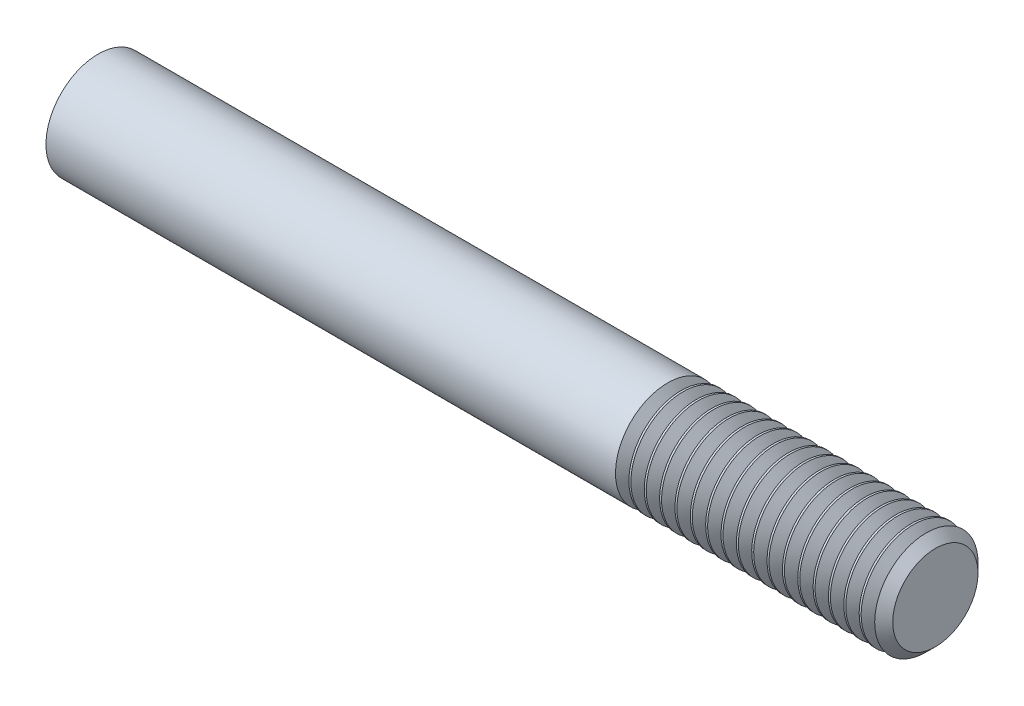
SolidWorks part; units mm, degrees
extrude "BaseHead" add sketch "Sketch1" along normal blind 0.254
sketch "Sketch1" plane through (0, 0, 0) normal (1, 0, 0) x (0, 0, -1)
  line L0 (6.35, 3.6662) -> (6.35, -3.6662)
  line L1 (-6.35, 3.6662) -> (-6.35, -3.6662)
  line L2 (6.35, -3.6662) -> (0, -7.3323)
  line L3 (0, -7.3323) -> (-6.35, -3.6662)
  line L4 (6.35, 3.6662) -> (0, 7.3323)
  line L5 (0, 7.3323) -> (-6.35, 3.6662)
  dimension "Width_flats" = 12.7
  dimension "D2" = 120
  dimension "D3" = 6.35
  dimension "D4" = 6.35
  dimension "D5" = 6.35
revolve "HeadChamfer" cut sketch "Sketch3" angle 360 about L6 other way angle 60
sketch "Sketch3" plane through (0, 0, 0) normal (0, 0, 1) x (1, 0, 0)
  line L0 (0, 6.35) -> (4.2333, 13.6823)
  line L1 (0, 7.3323) -> (0, 3.6662) construction
  line L2 (4.2333, 13.6823) -> (4.2333, 20.0323)
  line L3 (4.2333, 20.0323) -> (-12.7, 20.0323)
  line L4 (-12.7, 20.0323) -> (-12.7, 6.35)
  line L5 (-12.7, 6.35) -> (0, 6.35)
  line L6 (0, 0) -> (99.06, 0) construction
  line L7 (0.254, 7.3323) -> (0, 7.3323) construction
  dimension "D4" = 6.35
  dimension "D1" = 6.35
  dimension "D2" = 6.35
  dimension "D3" = 12.7
  dimension "Head_ch_ang" = 30
ref_plane "Plane1" through (0, 0, 0) normal (0, 0, 1) x (1, 0, 0)
ref_plane "Plane2" through (0, 0, 0) normal (0, 1, 0) x (1, 0, 0)
ref_plane "Plane3" through (0, 0, 0) normal (1, 0, 0) x (0, 0, -1)
sketch "BodySke" plane through (0, 0, 0) normal (0, 0, 1) x (1, 0, 0)
  line L0 (0, 3.6662) -> (0, -3.6662) construction
  line L1 (0, 0) -> (101.854, 0)
  line L2 (0, 0) -> (0, 6.35)
  line L3 (0, 6.35) -> (100.6907, 6.35)
  line L4 (101.854, 0) -> (101.854, 5.1867)
  line L5 (0.254, 7.3323) -> (0.254, 3.6662) construction
  line L6 (101.854, 5.1867) -> (100.6907, 6.35)
  line L7 (0, 0) -> (96.52, 0) construction
  line L8 (101.854, -5.1867) -> (100.6907, -6.35) construction
  line L9 (0, -6.35) -> (100.6907, -6.35) construction
  line L10 (2.2073, 15.24) -> (2.2073, -1.27) construction
  line L11 (70.104, 15.24) -> (70.104, -1.27) construction
  line L12 (0.254, 3.6662) -> (0.254, -3.6662) construction
  dimension "Diameter" = 12.7
revolve "BaseBody" add sketch "BodySke" angle 360 about L7
cosmetic thread "ThreadCosmetic" [suppressed] parameters "Thread_length"=31.75, "Thread_minor"=10.3734
sketch "Sketch4" plane through (0, 0, 0) normal (0, 0, 1) x (1, 0, 0)
  line L1 (0.254, 7.3323) -> (0.254, 3.6662) construction
  line L2 (0.254, 6.35) -> (-0.127, 6.35)
  line L3 (0.254, 6.35) -> (0.254, 32.7323)
  line L4 (0.254, 32.7323) -> (-0.127, 32.7323)
  line L5 (0, 0) -> (95.25, 0) construction
  line L6 (0, 0) -> (96.52, 0) construction
  line L7 (-0.127, 6.35) -> (-0.127, 32.7323)
  line L8 (0.5672, 7.3323) -> (0.254, 7.3323) construction
  dimension "D1" = 6.35
  dimension "D2" = 25.4
revolve "BearingFace" cut sketch "Sketch4" angle 360 about L5
sketch "ThdSchSke" plane through (0, 0, 0) normal (0, 0, 1) x (1, 0, 0)
  line L0 (70.104, -5.1867) -> (69.2894, -6.35)
  line L1 (70.104, -5.1867) -> (70.9186, -6.35)
  line L2 (70.9186, -6.35) -> (70.9186, -7.9375)
  line L3 (-3.175, 0) -> (5.1513, 0) construction
  line L5 (70.9186, -7.9375) -> (69.2894, -7.9375)
  line L6 (69.2894, -7.9375) -> (69.2894, -6.35)
  dimension "Thread_minor" = 10.3734
  dimension "Diameter" = 12.7
  dimension "Start" = 70.104
revolve "ThreadSchematic" cut sketch "ThdSchSke" angle 360 about L3
pattern_linear "ThdSchPat" count 17 spacing 1.8676 along (1, 0, 0) of "ThreadSchematic"
sketch "Croquis1" plane through (0, 0, 0) normal (-1, 0, 0) x (0, 0, 1)
  line L0 (-1.905, 2.54) -> (1.905, 2.54)
  arc A0 (-1.905, 2.54) -> (1.905, 2.54) centre (0, 0) ccw
  point P5 (0, 0)
  point P6 (0, 0)
  dimension "D1" = 6.35
  dimension "D2" = 2.54
extrude "Cortar-Extruir1" cut sketch "Croquis1" against normal blind 53.34
equation "\"D3@Sketch1\" = \"Width_flats@Sketch1\" / 2"
equation "\"D4@Sketch1\" = \"D3@Sketch1\""
equation "\"D5@Sketch1\" = \"D4@Sketch1\""
equation "\"Thread_minor@ThreadCosmetic\" = \"Minor_dia@BodySke\""
equation "\"D1@Sketch3\" = \"Width_flats@Sketch1\" / 2"
equation "\"D1@Sketch4\" = \"Width_flats@Sketch1\" / 2"
equation "\"Thread_length@ThreadCosmetic\" = ((sgn( (\"Length@BodySke\" - \"Advance@BodySke\" ) - \"Thread_nom@BodySke\" )-1)*( (\"Length@BodySke\" - \"Advance@BodySke\" ) - \"Thread_nom@BodySke\" ))/-2+ \"Thread_nom@BodySke\""
equation "\"Thread_minor@ThdSchSke\" = \"Minor_dia@BodySke\""
equation "\"Diameter@ThdSchSke\" = \"Diameter@BodySke\""
equation "\"Overcut@ThdSchSke\" = \"Diameter@BodySke\" * 1.25"
equation "\"Start@ThdSchSke\" = \"Head_ht@BaseHead\" + \"Length@BodySke\" - \"Thread_length@ThreadCosmetic\"  '---Non-countersunk---"
equation "\"Num_threads@ThdSchPat\" = int( \"Thread_length@ThreadCosmetic\" / \"Advance@BodySke\" + 0.999 )  + 1"
equation "\"Advance@ThdSchPat\" = \"Thread_length@ThreadCosmetic\" /  (\"Num_threads@ThdSchPat\" - 1) 'relax it"
equation "\"Num_threads@ThdSchPat\" = \"Num_threads@ThdSchPat\" - sgn( \"Num_threads@ThdSchPat\" - 1) '---chamfered tips only---"
